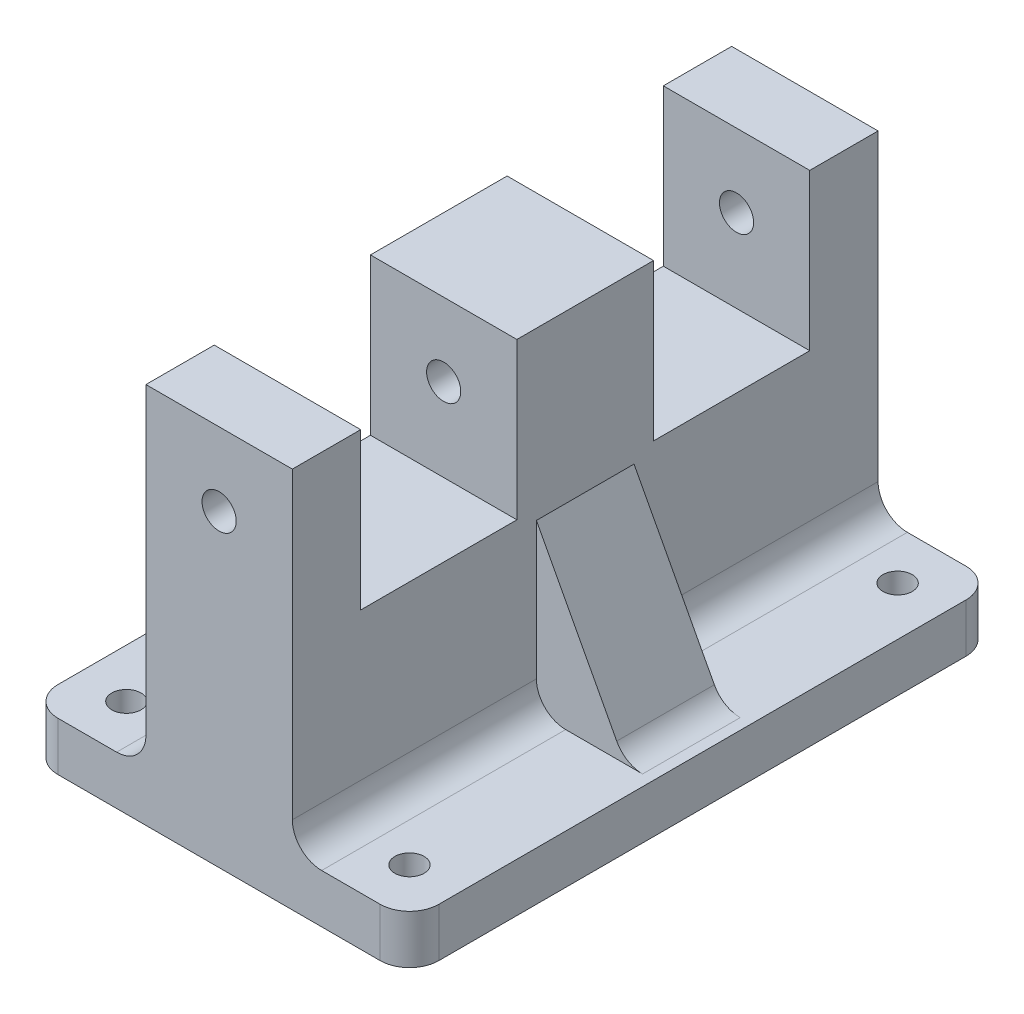
SolidWorks part; units mm, degrees
ref_plane "Front Plane" through (0, 0, 0) normal (0, 0, 1) x (1, 0, 0)
ref_plane "Top Plane" through (0, 0, 0) normal (0, 1, 0) x (1, 0, 0)
ref_plane "Right Plane" through (0, 0, 0) normal (1, 0, 0) x (0, 0, -1)
sketch "Sketch1" plane through (0, 0, 0) normal (0, 1, 0) x (1, 0, 0)
  line L1 (-7.5, 30) -> (7.5, 30)
  line L2 (-7.5, 30) -> (-7.5, -30)
  line L3 (-7.5, -30) -> (7.5, -30)
  line L4 (7.5, 30) -> (7.5, -30)
  line L5 (-7.5, 30) -> (7.5, -30) construction
  line L6 (-7.5, -30) -> (7.5, 30) construction
  point P0 (0, 0)
  dimension "D1" = 15
  dimension "D2" = 60
extrude "Boss-Extrude2" add sketch "Sketch1" along normal blind 39.11
sketch "Sketch3" plane through (-7.5, 0, 0) normal (-1, 0, 0) x (0, 0, 1)
  line L0 (-30, 0) -> (30, 0)
  line L1 (-30, 0) -> (-30, 5)
  line L2 (30, 0) -> (30, 5)
  line L3 (-30, 5) -> (30, 5)
  dimension "D1" = 5
extrude "Boss-Extrude3" add sketch "Sketch3" along normal blind 12 and the other way blind 27
ref_plane "Plane1" through (0, 0, 0) normal (0, 0, 1) x (1, 0, 0)
sketch "Sketch5" plane through (0, 0, 0) normal (0, 0, 1) x (1, 0, 0)
  line L0 (-7.5, 22.055) -> (-16.5741, 5)
  line L1 (-7.5, 39.11) -> (-7.5, 5) construction
  line L2 (-7.5, 5) -> (-19.5, 5) construction
rib "Rib1" sketch "Sketch5" sketch "Sketch5" thickness 10 extrusion direction parallel to sketch draft on no parameters "D1"=10
sketch "Sketch6" plane through (0, 5, 0) normal (0, 1, 0) x (1, 0, 0)
  line L0 (-19.5, -30) -> (-19.5, 30) construction
  line L1 (-7.5, -30) -> (-19.5, -30) construction
  line L2 (-18.15, 0) -> (18.15, 0) construction
  circle A0 centre (-14.5, -25) radius 1.5
  circle A1 centre (-14.5, 25) radius 1.5
  dimension "D1" = 3
  dimension "D2" = 5
  dimension "D3" = 5
extrude "Cut-Extrude2" cut sketch "Sketch6" against normal through all
mirror "Mirror1" about plane through (0, 0, 0) normal (1, 0, 0) of "Rib1", "Cut-Extrude2"
sketch "Sketch7" plane through (-7.5, 0, 0) normal (-1, 0, 0) x (0, 0, 1)
  line L0 (-30, 39.11) -> (30, 39.11) construction
  line L1 (7, 39.11) -> (23, 39.11)
  line L2 (7, 39.11) -> (7, 23.11)
  line L3 (7, 23.11) -> (23, 23.11)
  line L4 (23, 39.11) -> (23, 23.11)
  line L5 (7, 39.11) -> (23, 23.11) construction
  line L6 (7, 23.11) -> (23, 39.11) construction
  line L7 (30, 39.11) -> (30, 5) construction
  point P0 (15, 31.11)
  dimension "D1" = 16
  dimension "D2" = 16
  dimension "D3" = 7
extrude "Cut-Extrude3" cut sketch "Sketch7" against normal through all
mirror "Mirror2" about plane through (0, 0, 0) normal (0, 0, 1) of "Cut-Extrude3"
sketch "Sketch8" plane through (0, 0, -30) normal (0, 0, -1) x (-1, 0, 0)
  line L0 (-7.5, 39.11) -> (7.5, 39.11) construction
  circle A0 centre (0, 31.61) radius 1.75
  dimension "D2" = 3.5
  dimension "D1" = 7.5
extrude "Cut-Extrude4" cut sketch "Sketch8" against normal through all
fillet "Fillet1" radius 3 10 edges at (19.5, 2.5, -30) (19.5, 2.5, 30) (-19.5, 2.5, 30) (-19.5, 2.5, -30) (-16.5741, 5, 0) (-7.5, 5, -17.5) (-7.5, 5, 17.5) (16.5741, 5, 0) (7.5, 5, 17.5) (7.5, 5, -17.5)
